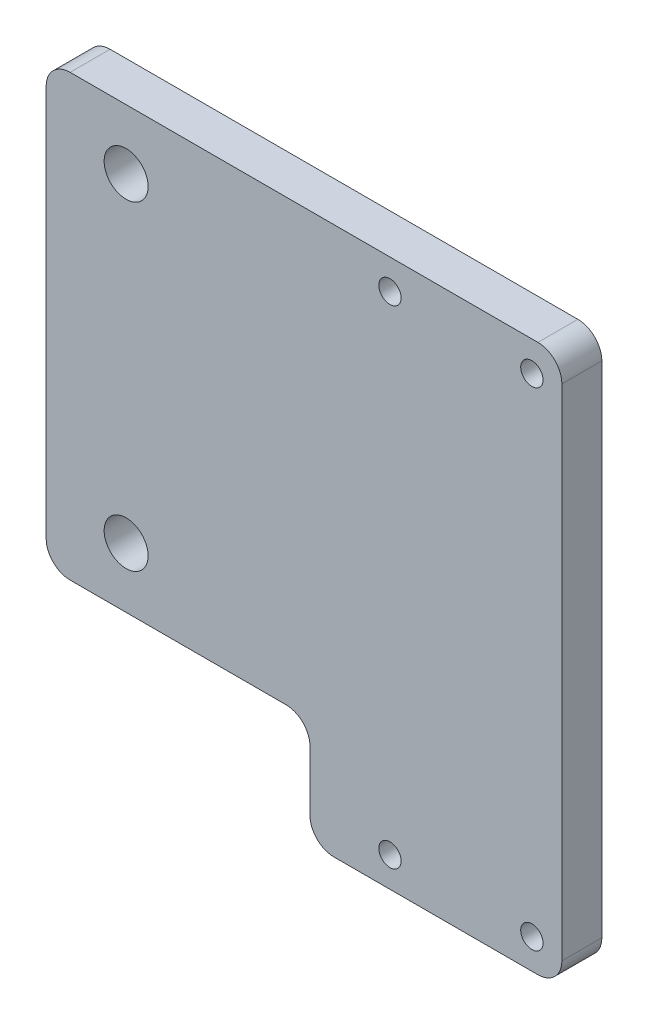
SolidWorks part; units mm, degrees
ref_plane "Front Plane" through (0, 0, 0) normal (0, 0, 1) x (1, 0, 0)
ref_plane "Top Plane" through (0, 0, 0) normal (0, 1, 0) x (1, 0, 0)
ref_plane "Right Plane" through (0, 0, 0) normal (1, 0, 0) x (0, 0, -1)
sketch "Base" plane through (0, 0, 0) normal (0, 0, 1) x (1, 0, 0)
  line L0 (0, 27.5) -> (-33, 27.5)
  line L1 (-33, 27.5) -> (-33, -27.5)
  line L2 (-33, -27.5) -> (0, -27.5)
  line L3 (0, -27.5) -> (0, -40.995)
  line L4 (0, -40.995) -> (24, -40.995)
  line L5 (24, -40.995) -> (24, 27.5) construction
  line L8 (-23, 20) -> (-23, -20) construction
  line L9 (12, -0.745) -> (12, -28.495) construction
  line L10 (19, -2.87) -> (5, -2.87) construction
  line L11 (19, -2.87) -> (19, -26.37) construction
  line L12 (19, -26.37) -> (5, -26.37) construction
  line L13 (5, -2.87) -> (5, -26.37) construction
  line L14 (0, 27.5) -> (24, 27.5)
  line L15 (24, 27.5) -> (31.5, 27.5)
  line L16 (31.5, 27.5) -> (31.5, -40.995)
  line L17 (31.5, -40.995) -> (24, -40.995)
  point P7 (24.1741, 0)
  point P9 (12, -40.995)
  point P10 (-33, 0)
  point P11 (-23, -20)
  point P12 (-23, 20)
  point P15 (-23, 0)
  point P20 (12, -2.87)
  point P21 (12, 40)
  point P22 (19, -14.62)
  point P23 (12, 20)
  point P24 (-23, -20)
  point P25 (-23, 20)
  point P26 (12, -0.745)
  point P27 (12, -28.495)
  point P30 (12, -14.62)
  point P31 (12, -20)
  dimension "D2" = 23.5
  dimension "D1" = 14
  dimension "D4" = 35
  dimension "D9" = 27.75
  dimension "D3" = 40
  dimension "D10" = 6.37
  dimension "D7" = 12.5
  dimension "D5" = 10
  dimension "D6" = 7.5
  dimension "D8" = 5
  dimension "D11" = 7.5
sketch "Hole_sketch" plane through (0, 0, 0) normal (0, 0, 1) x (1, 0, 0)
  point P0 (-23, -20)
  point P2 (-23, 20)
  point P4 (12, -0.745)
  point P6 (12, -28.495)
extrude "Main" add sketch "Base" along normal blind 5
hole_wizard "Gear Axis Holes" positions "Sketch9" profile "Sketch8" hole size "Ø5.5" standard "ANSI Metric" end condition through all
sketch "Sketch9" plane through (0, 0, 0) normal (0, 0, -1) x (-1, 0, 0)
  point P0 (23, -20)
  point P3 (23, 20)
sketch "Sketch8" plane through (-23, -20, 0) normal (1, 0, 0) x (0, 1, 0)
  line L0 (0, 0) -> (0, 5)
  line L1 (0, 5) -> (2.75, 5)
  line L2 (2.75, 5) -> (2.75, 0)
  line L5 (2.75, 0) -> (0, 0)
  line L11 (0, -6.35) -> (0, 107.95) construction
  dimension "Thru Hole Dia." = 5.5
  dimension "Thru Hole Depth" = 5
sketch "Sketch13" plane through (0, 0, 5) normal (0, 0, 1) x (1, 0, 0)
  line L0 (5, -2.87) -> (5, -26.37) construction
  line L1 (5, 27.5) -> (5, 20)
  line L2 (31.5, 27.5) -> (-33, 27.5) construction
  line L3 (5, 20) -> (24, 20)
  line L4 (24, 20) -> (24, -33.495)
  line L5 (24, -33.495) -> (5, -33.495)
  line L6 (5, -33.495) -> (5, -40.995)
  line L7 (5, -40.995) -> (31.5, -40.995)
  line L8 (31.5, -40.995) -> (31.5, 27.5)
  line L9 (31.5, 27.5) -> (5, 27.5)
  line L10 (0, -40.995) -> (31.5, -40.995) construction
  line L11 (31.5, -40.995) -> (31.5, 27.5) construction
  line L12 (24, -40.995) -> (24, 27.5) construction
  line L14 (24, -6.7475) -> (31.5, -6.7475) construction
  point P20 (10, 23.75)
  point P21 (27.75, 23.75)
  point P22 (27.75, -37.245)
  point P23 (10, -37.245)
  point P24 (27.75, -6.7475)
  point P25 (5, 23.75)
  point P26 (5, -37.245)
  dimension "D1" = 5
fillet "Fillet1" radius 3 6 edges at (0, -40.995, 2.5) (0, -27.5, 2.5) (-33, -27.5, 2.5) (-33, 27.5, 2.5) (31.5, 27.5, 2.5) (31.5, -40.995, 2.5)
hole_wizard "#3 Clearance Hole1" positions "Sketch15" profile "Sketch14" hole size "#3" standard "ANSI Inch" end condition through all
sketch "Sketch15" plane through (0, 0, 5) normal (0, 0, 1) x (1, 0, 0)
  point P0 (10, 23.75)
  point P3 (27.75, 23.75)
  point P6 (27.75, -37.245)
  point P9 (10, -37.245)
sketch "Sketch14" plane through (10, 23.75, 5) normal (1, 0, 0) x (0, -1, 0)
  line L0 (0, 0) -> (0, 5)
  line L1 (0, 5) -> (1.397, 5)
  line L2 (1.397, 5) -> (1.397, 0)
  line L5 (1.397, 0) -> (0, 0)
  line L11 (0, -6.35) -> (0, 107.95) construction
  dimension "Thru Hole Dia." = 2.794
  dimension "Thru Hole Depth" = 5
equation "\"D_gear-axes\"= 40mm"
equation "\"D_gear-servo\"= 35mm"
equation "\"W_servo\"= 23mm"
equation "\"W_servo-center\"= 6.37mm"
equation "\"D1@Base\"=\"L_servo\"+1"
equation "\"D2@Base\"=\"W_servo\"+0.5"
equation "\"L_servo\"= 13mm"
equation "\"D4@Base\" = \"D_gear-servo\""
equation "\"D9@Base\"=27.75"
equation "\"D_servo-holes\"= 3.1mm"
equation "\"D3@Base\"=\"D_gear-axes\""
equation "\"D10@Base\"=\"W_servo-center\""
